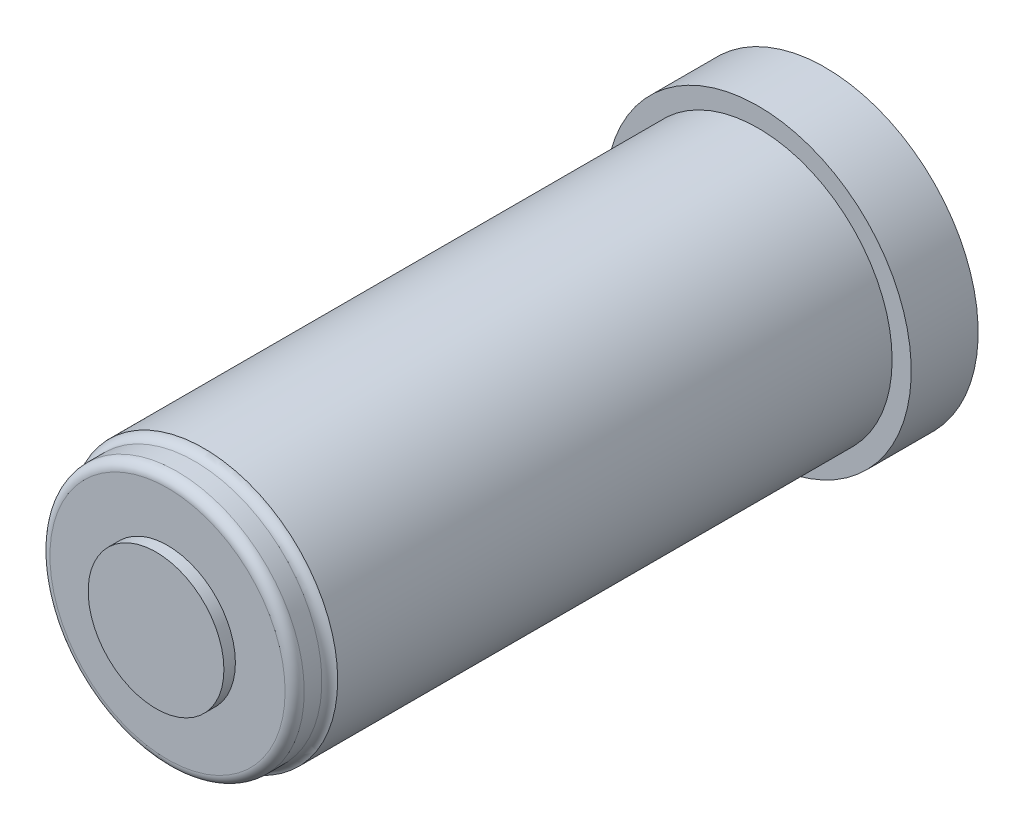
SolidWorks part; units mm, degrees
ref_plane "Front Plane" through (0, 0, 0) normal (0, 0, 1) x (1, 0, 0)
ref_plane "Top Plane" through (0, 0, 0) normal (0, 1, 0) x (1, 0, 0)
ref_plane "Right Plane" through (0, 0, 0) normal (1, 0, 0) x (0, 0, -1)
sketch "Sketch1" plane through (0, 0, 0) normal (0, 0, 1) x (1, 0, 0)
  circle A0 centre (0, 0) radius 140
  dimension "D1" = 280
extrude "Boss-Extrude1" add sketch "Sketch1" against normal blind 580
sketch "Sketch2" plane through (0, 0, 0) normal (0, 0, 1) x (1, 0, 0)
  circle A0 centre (0, 0) radius 133
extrude "Boss-Extrude2" add sketch "Sketch2" along normal blind 38
sketch "Sketch3" plane through (0, 0, 38) normal (0, 0, 1) x (1, 0, 0)
  circle A0 centre (0, 0) radius 71
extrude "Boss-Extrude3" add sketch "Sketch3" along normal blind 12
fillet "Fillet2" radius 10 2 edges at (133, 0, 0) (133, 0, 38)
sketch "Sketch4" plane through (0, 0, -580) normal (0, 0, -1) x (-1, 0, 0)
  circle A0 centre (0, 0) radius 160
  dimension "D1" = 320
extrude "Boss-Extrude4" add sketch "Sketch4" along normal blind 70
sketch "Sketch5" plane through (0, 0, -650) normal (0, 0, -1) x (-1, 0, 0)
  circle A0 centre (0, 0) radius 68.74
extrude "Cut-Extrude1" cut sketch "Sketch5" against normal blind 14
fillet "Fillet3" radius 10 1 edges at (-68.74, 0, -650)
